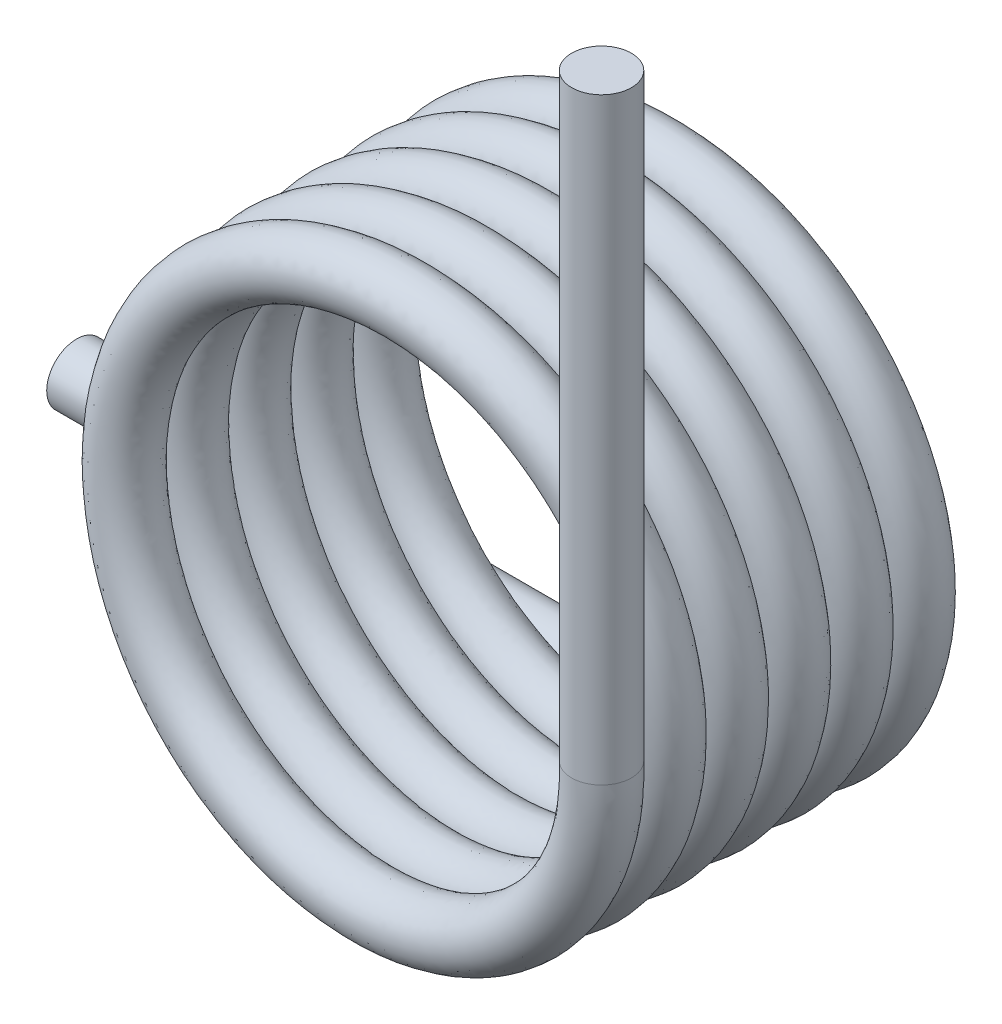
SolidWorks part; units mm, degrees
note: '?' marks a value the reader was unsure of.
ref_plane "Front" through (0, 0, 0) normal (0, 0, 1) x (1, 0, 0)
ref_plane "Top" through (0, 0, 0) normal (0, 1, 0) x (1, 0, 0)
ref_plane "Right" through (0, 0, 0) normal (1, 0, 0) x (0, 0, -1)
sketch "Sketch1" plane through (0, 0, 0) normal (0, 0, 1) x (1, 0, 0)
  circle A0 centre (0, 0) radius 2.55
  circle A1 centre (0, 0) radius 2.25 construction
  circle A2 centre (0, 2.55) radius 0.3 construction
  dimension "D1" = 0.6
  dimension "D2" = 4.5
curve "Helix/Spiral1" pitch 0.625 height 3.2812 turns 5.25
sketch "Sketch2" plane through (0, 0, 0) normal (0, 1, 0) x (1, 0, 0)
  circle A0 centre (2.55, 0) radius 0.3
  dimension "D1" = 0.6
sweep "Sweep1" add profiles "Sketch2" path "Helix/Spiral1"
sketch "Sketch4" plane through (0, 0, 0) normal (-1, 0, 0) x (0, -1, 0)
  circle A7 centre (2.55, -3.2813) radius 0.3
  circle A11 centre (2.55, -3.2813) radius 0.3
  dimension "D1" = 0
extrude "Boss-Extrude1" add sketch "Sketch4" along normal blind 6
sketch "Sketch5" plane through (0, 0, 0) normal (0, 1, 0) x (1, 0, 0)
  circle A5 centre (2.55, 0) radius 0.3
  circle A9 centre (2.55, 0) radius 0.3
  dimension "D1" = 0
extrude "Boss-Extrude2" add sketch "Sketch5" along normal blind 6
sketch "Sketch11" plane through (0, 0, 0) normal (1, 0, 0) x (0, 0, -1)
  line L0 (0, 0) -> (3.2813, 0)
  line L2 (1.6406, 0) -> (1.6406, 5.2574)
  line L3 (3.2813, -2.55) -> (3.2813, 0) construction
ref_plane "Plane1" through (0, 0, -1.6406) normal (0, 0, 1) x (1, 0, 0)
ref_axis "Axis1" through (2.55, 6, 0) along (0, -1, 0)?
ref_axis "Axis2" through (-6, -2.55, -3.2813) along (1, 0, 0)?
ref_plane "Plane2" through (0, 0, -1.6406) normal (0, 0, 1) x (1, 0, 0)
